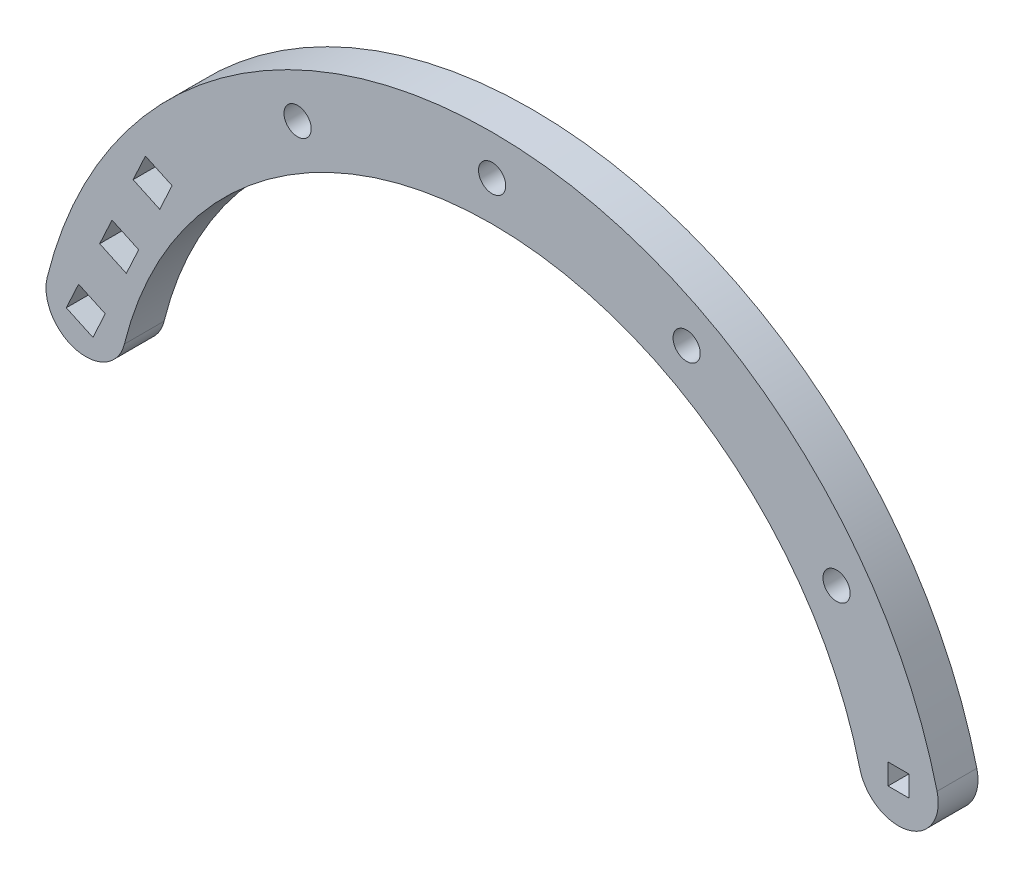
SolidWorks part; units mm, degrees
material "ABS"
ref_plane "Front Plane" through (0, 0, 0) normal (0, 0, 1) x (1, 0, 0)
ref_plane "Top Plane" through (0, 0, 0) normal (0, 1, 0) x (1, 0, 0)
ref_plane "Right Plane" through (0, 0, 0) normal (1, 0, 0) x (0, 0, -1)
sketch "Sketch2" plane through (0, 0, 0) normal (0, 0, 1) x (1, 0, 0)
  line L0 (0, 0) -> (10.6688, 23.0507) construction
  line L1 (-1.1425, 3.1113) -> (3.1113, 1.1425)
  line L2 (128.1049, 1.6637) -> (131.4323, 1.6637)
  line L3 (128.1049, 1.6637) -> (128.1049, -1.6637)
  line L4 (128.1049, -1.6637) -> (131.4323, -1.6637)
  line L5 (131.4323, 1.6637) -> (131.4323, -1.6637)
  line L6 (128.1049, 1.6637) -> (131.4323, -1.6637) construction
  line L7 (128.1049, -1.6637) -> (131.4323, 1.6637) construction
  line L8 (-1.1425, 3.1113) -> (-3.1113, -1.1425)
  line L9 (-3.1113, -1.1425) -> (1.1425, -3.1113)
  line L10 (3.1113, 1.1425) -> (1.1425, -3.1113)
  line L11 (-1.1425, 3.1113) -> (1.1425, -3.1113) construction
  line L12 (-3.1113, -1.1425) -> (3.1113, 1.1425) construction
  line L13 (4.1919, 14.6367) -> (2.2231, 10.3829)
  line L14 (4.1919, 14.6367) -> (8.4458, 12.6679)
  line L15 (8.4458, 12.6679) -> (6.4769, 8.414)
  line L16 (2.2231, 10.3829) -> (6.4769, 8.414)
  line L17 (9.5263, 26.1621) -> (7.5575, 21.9082)
  line L18 (9.5263, 26.1621) -> (13.7802, 24.1932)
  line L19 (13.7802, 24.1932) -> (11.8113, 19.9394)
  line L20 (7.5575, 21.9082) -> (11.8113, 19.9394)
  line L21 (7.5575, 21.9082) -> (13.7802, 24.1932) construction
  line L22 (9.5263, 26.1621) -> (11.8113, 19.9394) construction
  line L23 (2.2231, 10.3829) -> (8.4458, 12.6679) construction
  line L24 (4.1919, 14.6367) -> (6.4769, 8.414) construction
  arc A0 (129.7686, 0) -> (0, 0) centre (64.8843, -16.0367) ccw construction
  arc A1 (135.9331, 1.5236) -> (-6.1645, 1.5236) centre (64.8843, -16.0367) ccw
  arc A2 (123.6041, -1.5236) -> (6.1645, -1.5236) centre (64.8843, -16.0367) ccw
  arc A3 (123.6041, -1.5236) -> (135.9331, 1.5236) centre (129.7686, 0) ccw
  arc A4 (-6.1645, 1.5236) -> (6.1645, -1.5236) centre (0, 0) ccw
  circle A5 centre (0, 0) radius 2.2951 construction
  circle A6 centre (129.7686, 0) radius 2.5 construction
  point P0 (0, 0)
  point P1 (129.7686, 0)
  point P7 (64.8843, 50.8)
  point P23 (5.3344, 11.5254)
  point P24 (10.6688, 23.0507)
  dimension "D3" = 4.5901
  dimension "D4" = 5
  dimension "D1" = 129.7686
  dimension "D2" = 6.35
  dimension "D5" = 3.3274
  dimension "D6" = 50.8
  dimension "D7" = 25.4
  dimension "D8" = 4.6874
  dimension "D10" = 12.7
  dimension "D9" = 12.7
extrude "Boss-Extrude1" add sketch "Sketch2" along normal blind 6.35
sketch "Sketch4" plane through (0, 0, 6.35) normal (0, 0, 1) x (1, 0, 0)
  point P0 (64.8843, 50.8)
sketch "Sketch5" plane through (0, 0, 0) normal (0, 0, -1) x (-1, 0, 0)
  circle A0 centre (-64.8843, 50.8) radius 2.1717
  circle A1 centre (-33.8237, 43.1443) radius 2.1717
  circle A2 centre (-9.8787, 21.9309) radius 2.1717
  circle A3 centre (1.4651, -7.9805) radius 2.1717
  circle A4 centre (-2.3909, -39.7374) radius 2.1717
  circle A5 centre (-20.5633, -66.0648) radius 2.1717
  circle A6 centre (-48.8892, -80.9313) radius 2.1717
  circle A7 centre (-80.8794, -80.9313) radius 2.1717
  circle A8 centre (-109.2053, -66.0648) radius 2.1717
  circle A9 centre (-127.3777, -39.7374) radius 2.1717
  circle A10 centre (-131.2337, -7.9805) radius 2.1717
  circle A11 centre (-119.8899, 21.9309) radius 2.1717
  circle A12 centre (-95.9449, 43.1443) radius 2.1717
  dimension "D1" = 4.3434
  dimension "D2" = 13
extrude "Cut-Extrude1" cut sketch "Sketch5" against normal blind 25.4 contours A11 | A0 | A12 | A1
